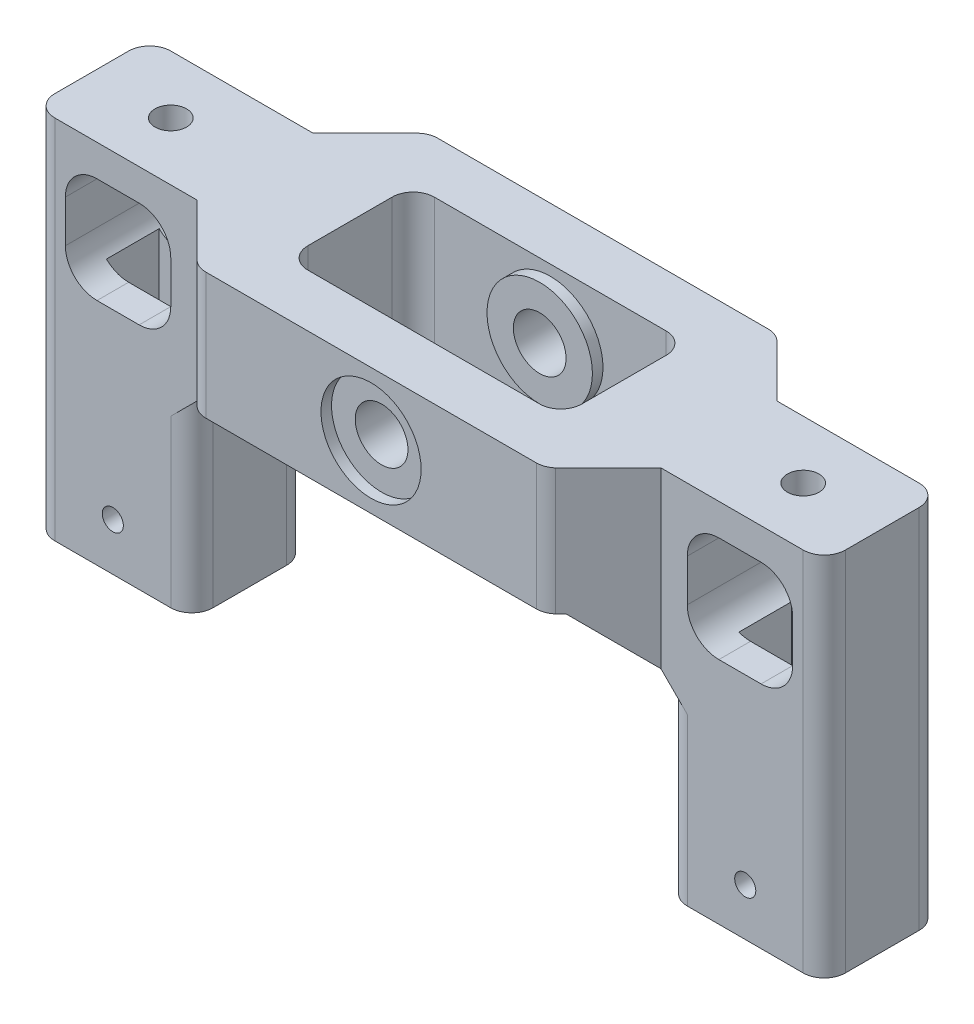
SolidWorks part; units mm, degrees
material "聚脂树脂"
ref_plane "前视基准面" through (0, 0, 0) normal (0, 0, 1) x (1, 0, 0)
ref_plane "上视基准面" through (0, 0, 0) normal (0, 1, 0) x (1, 0, 0)
ref_plane "右视基准面" through (0, 0, 0) normal (1, 0, 0) x (0, 0, -1)
other "Configuration Table"
sketch "草图1" plane through (0, 0, 0) normal (0, 0, 1) x (1, 0, 0)
  line L0 (0, 0) -> (63.4535, 0) construction
  line L5 (-22.5, 12.25) -> (-37.5, -12.25) construction
  line L6 (22.5, -12.25) -> (37.5, -12.25)
  line L7 (0, 0) -> (0, 35.1803) construction
  line L8 (22.5, -12.25) -> (22.5, 12.25)
  line L9 (22.5, 12.25) -> (37.5, 12.25)
  line L10 (37.5, -12.25) -> (37.5, 12.25)
  line L11 (22.5, -12.25) -> (37.5, 12.25) construction
  line L12 (22.5, 12.25) -> (37.5, -12.25) construction
  line L13 (-22.5, -12.25) -> (-37.5, 12.25) construction
  line L14 (-37.5, -12.25) -> (-37.5, 12.25)
  line L15 (-22.5, 12.25) -> (-37.5, 12.25)
  line L16 (-22.5, -12.25) -> (-22.5, 12.25)
  line L17 (-22.5, -12.25) -> (-37.5, -12.25)
  point P0 (30, 0)
  point P21 (-30, 0)
  dimension "D3" = 30
  dimension "D1" = 15
  dimension "D2" = 24.5
extrude "凸台-拉伸1" add sketch "草图1" along normal blind 5.5 and the other way blind 5.5
sketch "草图2" plane through (0, 12.25, 0) normal (0, 1, 0) x (1, 0, 0)
  line L0 (0, 0) -> (0, 28.9204) construction
  line L1 (0, 0) -> (49.6088, 0) construction
  line L2 (-26.4, 2.5) -> (-33.6, -2.5) construction
  line L3 (26.4, -2.5) -> (33.6, -2.5)
  line L4 (26.4, -2.5) -> (26.4, 2.5)
  line L5 (26.4, 2.5) -> (33.6, 2.5)
  line L6 (33.6, -2.5) -> (33.6, 2.5)
  line L7 (26.4, -2.5) -> (33.6, 2.5) construction
  line L8 (26.4, 2.5) -> (33.6, -2.5) construction
  line L9 (-26.4, -2.5) -> (-33.6, 2.5) construction
  line L10 (-33.6, -2.5) -> (-33.6, 2.5)
  line L11 (-26.4, 2.5) -> (-33.6, 2.5)
  line L12 (-26.4, -2.5) -> (-26.4, 2.5)
  line L13 (-26.4, -2.5) -> (-33.6, -2.5)
  point P3 (30, 0)
  point P13 (-30, 0)
  dimension "D1" = 7.2
  dimension "D2" = 5
  dimension "D3" = 30
extrude "切除-拉伸1" cut sketch "草图2" against normal blind 62
sketch "草图3" plane through (0, 12.25, 0) normal (0, 1, 0) x (1, 0, 0)
  line L0 (0, 0) -> (46.7542, 0) construction
  line L1 (0, 0) -> (0, 26.73) construction
  line L2 (22.5, 5.5) -> (17, 5.5)
  line L3 (17, 5.5) -> (17, 11)
  line L4 (17, 11) -> (-17, 11)
  line L6 (-13, 6) -> (13, 6)
  line L7 (13, 6) -> (13, -6)
  line L8 (22.5, 5.5) -> (22.5, -5.5)
  line L9 (22.5, 5.5) -> (22.5, -5.5) construction
  line L10 (-13, -6) -> (13, -6)
  line L12 (17, -11) -> (-17, -11)
  line L13 (17, -5.5) -> (17, -11)
  line L14 (22.5, -5.5) -> (17, -5.5)
  line L15 (-22.5, -5.5) -> (-17, -5.5)
  line L16 (-17, -5.5) -> (-17, -11)
  line L17 (-22.5, 5.5) -> (-22.5, -5.5)
  line L18 (-13, 6) -> (-13, -6)
  line L19 (-17, 5.5) -> (-17, 11)
  line L20 (-22.5, 5.5) -> (-17, 5.5)
  point P16 (22.5, 0)
  point P17 (13, 0)
  point P24 (0, -11)
  point P25 (0, -6)
  point P27 (0, 6)
  point P28 (0, 11)
  point P29 (-13, 0)
  point P30 (-22.5, 0)
  dimension "D1" = 12
  dimension "D2" = 26
  dimension "D3" = 34
  dimension "D4" = 22
extrude "凸台-拉伸2" add sketch "草图3" against normal blind 12
sketch "草图4" plane through (0, 0, 11) normal (0, 0, 1) x (1, 0, 0)
  line L0 (0, 0) -> (0, 29.922) construction
  line L1 (-17, 0.25) -> (17, 0.25) construction
  circle A0 centre (0, 6.25) radius 2.5
  dimension "D1" = 5
  dimension "D2" = 6
extrude "切除-拉伸2" cut sketch "草图4" against normal blind 90
sketch "草图6" plane through (0, 0, 5.5) normal (0, 0, 1) x (1, 0, 0)
  line L0 (0, 0) -> (0, 28.8184) construction
  line L1 (0, 0) -> (51.072, 0) construction
  line L2 (-37.5, 12.25) -> (-37.5, 24.25)
  line L3 (-37.5, 24.25) -> (-16, 24.25)
  line L4 (-16, 24.25) -> (-16, 12.25)
  line L5 (-37.5, 12.25) -> (-17, 12.25) construction
  line L7 (-35, 12.25) -> (-35, 21.75)
  line L8 (-35, 21.75) -> (-18.5, 21.75)
  line L9 (-18.5, 21.75) -> (-18.5, 12.25)
  line L10 (-37.5, 12.25) -> (-35, 12.25)
  line L11 (-18.5, 12.25) -> (-16, 12.25)
  line L12 (18.5, 21.75) -> (18.5, 12.25)
  line L13 (35, 21.75) -> (18.5, 21.75)
  line L14 (35, 12.25) -> (35, 21.75)
  line L15 (37.5, 12.25) -> (35, 12.25)
  line L16 (37.5, 12.25) -> (37.5, 24.25)
  line L17 (37.5, 24.25) -> (16, 24.25)
  line L18 (16, 24.25) -> (16, 12.25)
  line L19 (18.5, 12.25) -> (16, 12.25)
  line L20 (37.5, 12.25) -> (17, 12.25) construction
  dimension "D1" = 12
  dimension "D3" = 32
  dimension "D2" = 2.5
chamfer "倒角2" distance 5 angle 45 4 edges at (17, 6.25, -5.5) (-17, 6.25, -5.5) (17, 6.25, 5.5) (-17, 6.25, 5.5)
fillet "圆角2" radius 2 8 edges at (17, 6.25, 11) (-17, 6.25, 11) (-17, 6.25, -11) (17, 6.25, -11) (-13, 6.25, 6) (13, 6.25, 6) (13, 6.25, -6) (-13, 6.25, -6)
sketch "草图14" plane through (0, -12.25, 0) normal (0, -1, 0) x (1, 0, 0)
  line L0 (26.4, 2.5) -> (26.4, -2.5) construction
  line L1 (26.4, -2.5) -> (33.6, -2.5) construction
  line L2 (33.6, -2.5) -> (33.6, 2.5) construction
  line L3 (33.6, 2.5) -> (26.4, 2.5) construction
  line L4 (-22.5, -5.5) -> (-22.5, 5.5)
  line L5 (-22.5, 5.5) -> (-37.5, 5.5)
  line L6 (-37.5, 5.5) -> (-37.5, -5.5)
  line L7 (-37.5, -5.5) -> (-22.5, -5.5)
  line L8 (-22.5, -5.5) -> (-22.5, 5.5)
  line L9 (-22.5, 5.5) -> (-37.5, 5.5)
  line L10 (-37.5, 5.5) -> (-37.5, -5.5)
  line L11 (-37.5, -5.5) -> (-22.5, -5.5)
  line L12 (37.5, -5.5) -> (37.5, 5.5)
  line L13 (37.5, 5.5) -> (22.5, 5.5)
  line L14 (22.5, 5.5) -> (22.5, -5.5)
  line L15 (22.5, -5.5) -> (37.5, -5.5)
  line L16 (37.5, -5.5) -> (37.5, 5.5)
  line L17 (37.5, 5.5) -> (22.5, 5.5)
  line L18 (22.5, 5.5) -> (22.5, -5.5)
  line L19 (22.5, -5.5) -> (37.5, -5.5)
  line L20 (-26.4, -2.5) -> (-26.4, 2.5) construction
  line L21 (-33.6, -2.5) -> (-26.4, -2.5) construction
  line L22 (-33.6, 2.5) -> (-33.6, -2.5) construction
  line L23 (-26.4, 2.5) -> (-33.6, 2.5) construction
  line L24 (26.4, 2.5) -> (26.4, -2.5)
  line L25 (26.4, -2.5) -> (33.6, -2.5)
  line L26 (33.6, -2.5) -> (33.6, 2.5)
  line L27 (33.6, 2.5) -> (26.4, 2.5)
  line L28 (-26.4, -2.5) -> (-26.4, 2.5)
  line L29 (-33.6, -2.5) -> (-26.4, -2.5)
  line L30 (-33.6, 2.5) -> (-33.6, -2.5)
  line L31 (-26.4, 2.5) -> (-33.6, 2.5)
  dimension "D1" = 0
  dimension "D2" = 0
extrude "凸台-拉伸5" add sketch "草图14" along normal blind 10.25
sketch "草图7" plane through (0, 0, 5.5) normal (0, 0, 1) x (1, 0, 0)
  line L0 (0, 0) -> (0, 26.3753) construction
  line L1 (0, 1.8) -> (49.2666, 1.8) construction
  line L2 (0, 0) -> (53.2402, 0) construction
  circle A0 centre (30, -18) radius 1
  circle A3 centre (-30, -18) radius 1
  dimension "D1" = 60
  dimension "D2" = 18
  dimension "D3" = 2
  dimension "D6" = 2
  dimension "D7" = 30
  dimension "D4" = 1.8
  dimension "D5" = 30
extrude "切除-拉伸3" cut sketch "草图7" against normal blind 34
sketch "草图9" plane through (0, 0, 5.5) normal (0, 0, 1) x (1, 0, 0)
  line L6 (0, 0) -> (0, -19.4283) construction
sketch "草图13" plane through (0, 0, -6) normal (0, 0, 1) x (1, 0, 0)
  circle A0 centre (0, 6.25) radius 5
  circle A1 centre (0, 6.25) radius 2.5
  dimension "D1" = 5
  dimension "D2" = 10
extrude "凸台-拉伸4" add sketch "草图13" along normal blind 1
mirror "镜向1" about plane through (0, 0, 0) normal (0, 0, 1) of "凸台-拉伸4"
chamfer "倒角3" distance 5 angle 45 2 edges at (22.5, 0.25, 0) (-22.5, 0.25, 0)
sketch "草图17" plane through (0, 0, 11) normal (0, 0, 1) x (1, 0, 0)
  circle A0 centre (0, 6.25) radius 2.5
  circle A1 centre (0, 6.25) radius 4.75
  dimension "D1" = 5
  dimension "D2" = 9.5
sketch "草图19" plane through (0, 0, 5.5) normal (0, 0, 1) x (1, 0, 0)
  line L0 (-37.5, 12.25) -> (-37.5, -22.5) construction
  line L1 (-34.5, -0.75) -> (-24.5, -0.75)
  line L2 (-34.5, -0.75) -> (-34.5, 9.25)
  line L3 (-34.5, 9.25) -> (-24.5, 9.25)
  line L4 (-24.5, -0.75) -> (-24.5, 9.25)
  line L5 (-34.5, -0.75) -> (-24.5, 9.25) construction
  line L6 (-34.5, 9.25) -> (-24.5, -0.75) construction
  line L8 (0, 6.25) -> (0, 20.5388) construction
  line L9 (-37.5, 12.25) -> (-22, 12.25) construction
  line L10 (34.5, 9.25) -> (24.5, 9.25)
  line L11 (24.5, -0.75) -> (24.5, 9.25)
  line L12 (34.5, -0.75) -> (24.5, -0.75)
  line L13 (34.5, -0.75) -> (34.5, 9.25)
  point P0 (-29.5, 4.25)
  dimension "D1" = 10
  dimension "D2" = 10
  dimension "D3" = 3
  dimension "D4" = 3
extrude "切除-拉伸4" cut sketch "草图19" against normal blind 31.2 contours L3 L2 L1 L4 | L10 L11 L12 L13 region at (-29.5, 4.25, 5.5) region at (29.5, 4.25, 5.5)
extrude "切除-拉伸5" cut sketch "草图17" against normal blind 1
mirror "镜向2" about plane through (0, 0, 0) normal (0, 0, 1) of "切除-拉伸5"
sketch "草图20" plane through (0, 0, -2.5) normal (0, 0, 1) x (1, 0, 0)
  line L4 (-33.6, 12.25) -> (-33.6, 9.25)
  line L5 (-33.6, 9.25) -> (-26.4, 9.25)
  line L6 (-26.4, 9.25) -> (-26.4, 12.25)
  line L7 (-26.4, 12.25) -> (-33.6, 12.25)
  line L8 (-33.6, 12.25) -> (-33.6, 9.25)
  line L10 (-26.4, 9.25) -> (-26.4, 12.25)
  line L11 (-26.4, 12.25) -> (-33.6, 12.25)
  line L12 (26.4, 9.25) -> (33.6, 9.25)
  line L13 (33.6, 9.25) -> (33.6, 12.25)
  line L14 (33.6, 12.25) -> (26.4, 12.25)
  line L15 (26.4, 12.25) -> (26.4, 9.25)
  line L17 (33.6, 9.25) -> (33.6, 12.25)
  line L18 (33.6, 12.25) -> (26.4, 12.25)
  line L19 (26.4, 12.25) -> (26.4, 9.25)
  line L24 (-33.6, 9.25) -> (-26.4, 9.25)
  line L25 (26.4, 9.25) -> (33.6, 9.25)
  dimension "D1" = 0
  dimension "D2" = 0
extrude "凸台-拉伸6" add sketch "草图20" along normal up to surface (5 mm away) up to face at (-30, 10.75, 2.5)
fillet "圆角6" radius 3 8 edges at (24.5, -0.75, 0) (-24.5, -0.75, 0) (34.5, -0.75, 0) (24.5, 9.25, 0) (34.5, 9.25, 0) (-24.5, 9.25, 0) (-34.5, 9.25, 0) (-34.5, -0.75, 0)
fillet "圆角7" radius 2 8 edges at (-22.5, -13.625, 5.5) (-37.5, -5.125, 5.5) (-37.5, -5.125, -5.5) (-22.5, -13.625, -5.5) (22.5, -13.625, -5.5) (22.5, -13.625, 5.5) (37.5, -5.125, -5.5) (37.5, -5.125, 5.5)
sketch "草图23" plane through (0, 12.25, 0) normal (0, 1, 0) x (1, 0, 0)
  line L0 (0, 0) -> (47.0369, 0) construction
  line L1 (0, 0) -> (0, 25.265) construction
  circle A0 centre (30, 0) radius 1.5
  circle A1 centre (-30, 0) radius 1.5
  dimension "D1" = 3
  dimension "D2" = 60
extrude "切除-拉伸6" cut sketch "草图23" against normal blind 3
equation "\"5】\"=10"
